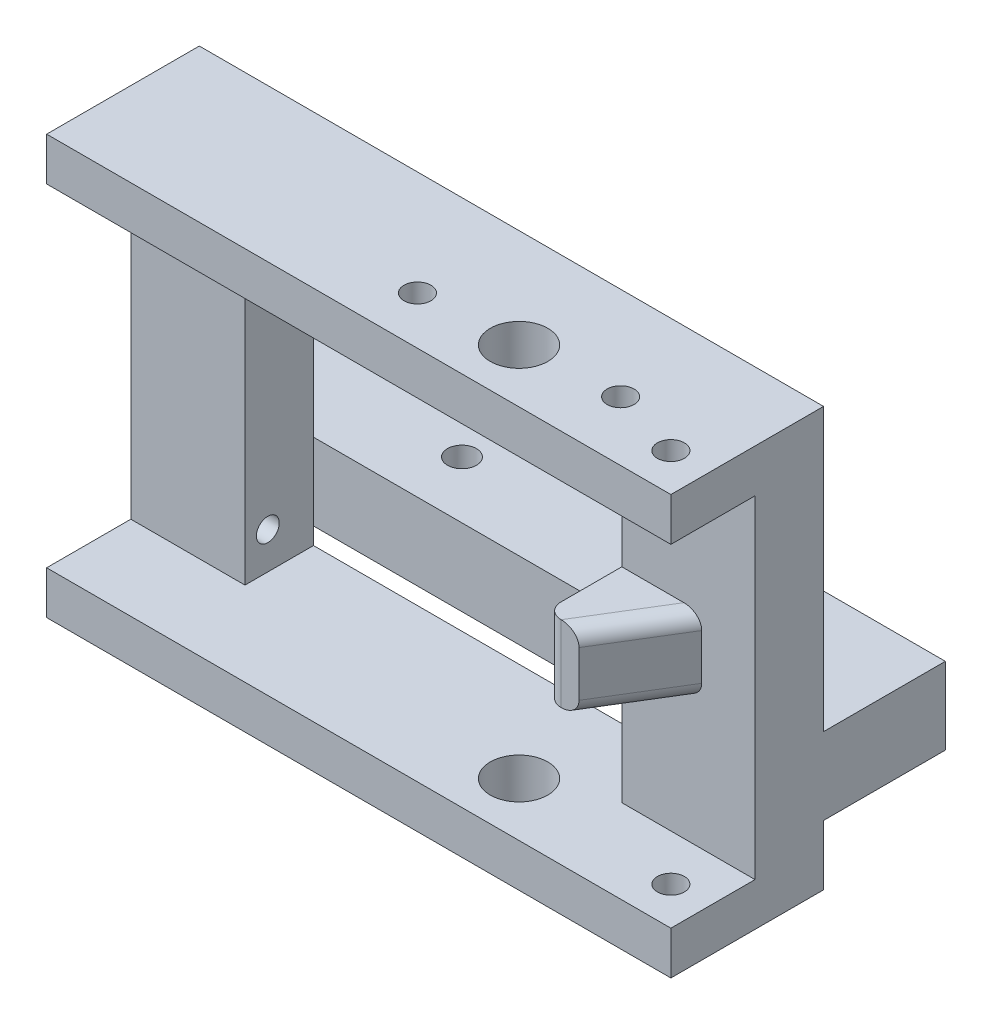
SolidWorks part; units mm, degrees
ref_plane "Front Plane" through (0, 0, 0) normal (0, 0, 1) x (1, 0, 0)
ref_plane "Top Plane" through (0, 0, 0) normal (0, 1, 0) x (1, 0, 0)
ref_plane "Right Plane" through (0, 0, 0) normal (1, 0, 0) x (0, 0, -1)
sketch "Sketch1" plane through (0, 0, 0) normal (0, 0, 1) x (1, 0, 0)
  line L1 (57.15, -34.925) -> (-57.15, -34.925)
  line L2 (57.15, -34.925) -> (57.15, 34.925)
  line L3 (57.15, 34.925) -> (-57.15, 34.925)
  line L4 (-57.15, -34.925) -> (-57.15, 34.925)
  line L5 (57.15, -34.925) -> (-57.15, 34.925) construction
  line L6 (57.15, 34.925) -> (-57.15, -34.925) construction
  point P0 (0, 0)
  dimension "D1" = 69.85
  dimension "D2" = 114.3
extrude "Boss-Extrude1" add sketch "Sketch1" along normal blind 57.15
sketch "Sketch2" plane through (0, 0, 57.15) normal (0, 0, 1) x (1, 0, 0)
  line L0 (-57.15, 34.925) -> (-57.15, -34.925) construction
  line L1 (57.15, -27.725) -> (-57.15, -27.725)
  line L2 (57.15, -27.725) -> (57.15, 27.725)
  line L3 (57.15, 27.725) -> (-57.15, 27.725)
  line L4 (-57.15, -27.725) -> (-57.15, 27.725)
  line L5 (57.15, -27.725) -> (-57.15, 27.725) construction
  line L6 (57.15, 27.725) -> (-57.15, -27.725) construction
  line L7 (57.15, 34.925) -> (-57.15, 34.925) construction
  point P0 (0, 0)
  dimension "D1" = 7.2
extrude "Cut-Extrude2" cut sketch "Sketch2" against normal blind 25.4
sketch "Sketch3" plane through (0, 0, 0) normal (0, 0, -1) x (-1, 0, 0)
  line L0 (-57.15, -34.925) -> (-57.15, 34.925) construction
  line L1 (57.15, 34.925) -> (-57.15, 34.925)
  line L2 (57.15, 34.925) -> (57.15, -12.065)
  line L3 (57.15, -12.065) -> (-57.15, -12.065)
  line L4 (-57.15, 34.925) -> (-57.15, -12.065)
  dimension "D1" = 46.99
extrude "Cut-Extrude3" cut sketch "Sketch3" against normal blind 20.32
sketch "Sketch5" plane through (0, -34.925, 0) normal (0, -1, 0) x (1, 0, 0)
  line L0 (-3.81, 10.79) -> (46.99, 10.79) construction
  line L1 (57.15, 20.32) -> (-57.15, 20.32) construction
  line L2 (57.15, 57.15) -> (57.15, 0) construction
  circle A0 centre (-3.81, 10.79) radius 2.415
  circle A1 centre (46.99, 10.79) radius 2.415
  dimension "D3" = 4.83
  dimension "D4" = 10.16
  dimension "D1" = 9.53
  dimension "D2" = 50.8
sketch "Sketch7" plane through (0, -34.925, 0) normal (0, -1, 0) x (1, 0, 0)
  line L0 (57.15, 57.15) -> (57.15, 0) construction
  line L2 (-57.15, 31.75) -> (57.15, 31.75) construction
  circle A0 centre (31.75, 36.83) radius 4.8
  dimension "D1" = 9.6
  dimension "D2" = 25.4
  dimension "D3" = 5.08
extrude "Cut-Extrude6" cut sketch "Sketch7" against normal up to surface (69.85 mm away) up to face at (0, 34.925, 38.735)
sketch "Sketch8" plane through (0, 34.925, 0) normal (0, 1, 0) x (1, 0, 0)
  line L0 (15.7798, -37.8068) -> (47.7202, -35.8532) construction
  line L1 (57.15, -31.75) -> (-57.15, -31.75) construction
  circle A0 centre (31.75, -36.83) radius 16 construction
  circle A1 centre (15.7798, -37.8068) radius 2.25
  circle A2 centre (47.7202, -35.8532) radius 2.25
  dimension "D1" = 32
  dimension "D2" = 4.5
  dimension "D3" = 3.5
sketch "Sketch9" plane through (0, 0, 31.75) normal (0, 0, 1) x (1, 0, 0)
  line L0 (57.15, 34.925) -> (-57.15, 34.925) construction
  line L5 (57.15, 27.725) -> (-57.15, 27.725) construction
  line L6 (-19.05, 27.725) -> (43.815, 27.725)
  line L7 (-19.05, 27.725) -> (-19.05, -27.725)
  line L8 (-19.05, -27.725) -> (43.815, -27.725)
  line L9 (43.815, 27.725) -> (43.815, -27.725)
  line L10 (-57.15, -27.725) -> (57.15, -27.725) construction
  line L11 (-57.15, 27.725) -> (-57.15, -27.725) construction
  line L12 (57.15, -27.725) -> (57.15, 27.725) construction
  line L13 (-57.15, -34.925) -> (-38.1, -34.925)
  line L14 (-57.15, -34.925) -> (-57.15, 34.925)
  line L15 (-57.15, 34.925) -> (-38.1, 34.925)
  line L16 (-38.1, -34.925) -> (-38.1, 34.925)
  line L17 (-57.15, -34.925) -> (-38.1, 34.925) construction
  line L18 (-57.15, 34.925) -> (-38.1, -34.925) construction
  line L19 (-57.15, -34.925) -> (57.15, -34.925) construction
  point P5 (-47.625, 0)
  dimension "D1" = 13.335
  dimension "25in" = 38.1
  dimension "D2" = 19.05
extrude "Cut-Extrude7" cut sketch "Sketch9" against normal through all both and the other way through all
extrude "Cut-Extrude8" cut sketch "Sketch8" against normal up to next
sketch "Sketch10" [suppressed] plane through (0, 0, 29.21) normal (0, 0, 1) x (1, 0, 0)
  line L1 (-30.607, -1.778) -> (-30.607, -6.604) construction
  circle A0 centre (-33.2489, -4.191) radius 2.286
  point P5 (-30.607, -4.191)
  dimension "D1" = 4.572
sketch "Sketch11" [suppressed] plane through (0, 0, 20.32) normal (0, 0, -1) x (-1, 0, 0)
  circle A0 centre (33.2489, -4.191) radius 2.286
  dimension "D1" = 4.572
extrude "Cut-Extrude9" [suppressed] cut sketch "Sketch11" against normal blind 3.81
sketch "Sketch12" plane through (-19.05, 0, 0) normal (1, 0, 0) x (0, 0, -1)
  line L0 (-31.75, -27.725) -> (-31.75, 27.725) construction
  line L1 (-27.94, -21.59) -> (-27.94, 21.59) construction
  line L2 (-20.32, 27.725) -> (-20.32, -12.065) construction
  circle A0 centre (-27.94, -21.59) radius 1.905
  circle A1 centre (-27.94, 21.59) radius 1.905
  point P0 (-31.75, 0)
  point P8 (-27.94, 0)
  dimension "D1" = 3.81
  dimension "D2" = 7.62
  dimension "D3" = 43.18
extrude "Cut-Extrude10" cut sketch "Sketch12" against normal up to surface (19.05 mm away) up to face at (-38.1, -2.413, 33.274)
sketch "Sketch13" plane through (0, 34.925, 0) normal (0, 1, 0) x (1, 0, 0)
  line L0 (-38.1, -45.7884) -> (57.15, -45.7884)
  line L2 (57.15, -57.15) -> (-38.1, -57.15) construction
  line L3 (47.7202, -35.8532) -> (15.7798, -37.8068) construction
  line L4 (-38.1, -45.7884) -> (-38.1, -57.15)
  line L5 (-38.1, -57.15) -> (57.15, -57.15)
  line L6 (-38.1, -20.32) -> (-38.1, -57.15) construction
  line L7 (57.15, -57.15) -> (57.15, -20.32) construction
  line L8 (57.15, -45.7884) -> (57.15, -57.15)
extrude "Cut-Extrude12" cut sketch "Sketch13" against normal through all
sketch "Sketch14" plane through (43.815, 0, 0) normal (-1, 0, 0) x (0, 0, 1)
  line L0 (0, -27.725) -> (31.75, -27.725) construction
  line L1 (20.32, -12.065) -> (0, -12.065)
  line L2 (20.32, -12.065) -> (20.32, -27.725)
  line L3 (20.32, -27.725) -> (0, -27.725)
  line L4 (0, -12.065) -> (0, -27.725)
extrude "Boss-Extrude2" add sketch "Sketch14" along normal up to next
sketch "Sketch16" plane through (0, 0, 31.75) normal (0, 0, 1) x (1, 0, 0)
  line L0 (43.815, -27.725) -> (43.815, 27.725) construction
  line L1 (57.15, -6.35) -> (43.815, -6.35)
  line L2 (57.15, -6.35) -> (57.15, 6.35)
  line L3 (57.15, 6.35) -> (43.815, 6.35)
  line L4 (43.815, -6.35) -> (43.815, 6.35)
  line L5 (57.15, -6.35) -> (43.815, 6.35) construction
  line L6 (57.15, 6.35) -> (43.815, -6.35) construction
  line L7 (57.15, 6.35) -> (57.15, -6.35) construction
  line L9 (57.15, -27.725) -> (57.15, 27.725) construction
  point P0 (50.4825, 0)
  point P7 (57.15, 0)
  dimension "D1" = 12.7
extrude "Boss-Extrude3" add sketch "Sketch16" along normal blind 12.7
sketch "Sketch17" plane through (0, 6.35, 0) normal (0, 1, 0) x (1, 0, 0)
  line L0 (49.375, -44.45) -> (57.15, -31.75)
  line L1 (57.15, -44.45) -> (57.15, -31.75) construction
  line L2 (57.15, -31.75) -> (43.815, -31.75) construction
  line L3 (57.15, -31.75) -> (57.15, -44.45)
  line L4 (57.15, -44.45) -> (49.375, -44.45)
  line L5 (57.15, -44.45) -> (43.815, -44.45) construction
extrude "Cut-Extrude14" cut sketch "Sketch17" against normal blind 12.7
fillet "Fillet4" radius 2.54 2 edges at (53.2625, -6.35, 38.1) (53.2625, 6.35, 38.1)
sketch "Sketch18" plane through (-38.1, 0, 0) normal (-1, 0, 0) x (0, 0, 1)
  line L0 (0, -34.925) -> (45.7884, -34.925) construction
  line L1 (20.32, -35.0627) -> (20.32, -24.9001)
  line L2 (20.32, -24.9001) -> (0, -24.9001)
  line L3 (0, -34.925) -> (0, -12.065) construction
  line L4 (0, -24.9001) -> (0, -34.925)
  line L5 (20.32, -34.925) -> (0, -34.925)
  point P0 (20.32, -34.925)
  point P1 (7.9478, 3.6724)
  line M3 (0, -34.925) -> (45.7884, -34.925)
  line M12 (0, -12.065) -> (0, -34.925)
sketch "Sketch19" plane through (-38.1, 0, 0) normal (-1, 0, 0) x (0, 0, 1)
  line L0 (20.32, -34.925) -> (0, -34.925)
sketch "Sketch20" plane through (-38.1, 0, 0) normal (-1, 0, 0) x (0, 0, 1)
  line L0 (0, -34.925) -> (45.7884, -34.925) construction
  line L1 (20.066, -34.925) -> (20.066, -24.765)
  line L2 (20.066, -24.765) -> (0, -24.765)
  line L3 (0, -34.925) -> (0, -12.065) construction
  line L4 (0, -24.765) -> (0, -34.925)
  line L5 (20.066, -34.925) -> (-0.1509, -34.925)
  point P0 (20.32, -34.925)
  dimension "D1" = 10.16
  dimension "D2" = 20.066
extrude "Cut-Extrude20" cut sketch "Sketch5" against normal through all contours A0 | A1
sketch "Sketch21" plane through (-38.1, 0, 0) normal (-1, 0, 0) x (0, 0, 1)
sketch "Sketch22" plane through (-38.1, 0, 0) normal (-1, 0, 0) x (0, 0, 1)
extrude "Cut-Extrude21" cut sketch "Sketch18" against normal through all contours L1 L2 M12 M3 region at (-38.1, -29.9125, 10.16)
sketch "Sketch23" plane through (0, -34.925, 0) normal (0, -1, 0) x (1, 0, 0)
  line L0 (57.15, 20.32) -> (57.15, 31.75)
  line L1 (57.15, 45.7884) -> (57.15, 20.32) construction
  circle A0 centre (52.07, 26.035) radius 2.413
  point P7 (57.15, 26.035)
  dimension "D2" = 4.826
  dimension "D1" = 11.43
  dimension "D3" = 5.08
sketch "Sketch24" plane through (0, 34.925, 0) normal (0, 1, 0) x (1, 0, 0)
  line L0 (47.7202, -35.8532) -> (15.7798, -37.8068)
  point P0 (47.7202, -35.8532)
  point P1 (15.7798, -37.8068)
sketch3d "3DSketch2"
  line L1 (47.7202, 34.925, 35.8532) -> (15.7798, 34.925, 37.8068) construction
fillet "Fillet5" radius 2.54 1 edges at (43.815, 0, 44.45)
sketch "Sketch26" plane through (57.15, 0, 0) normal (1, 0, 0) x (0, 0, -1)
  line L28 (-45.7884, -34.925) -> (-20.32, -34.925)
  line L29 (-20.32, -34.925) -> (-20.32, -24.9001)
  line L30 (-20.32, -24.9001) -> (0, -24.9001)
  line L31 (0, -24.9001) -> (0, -12.065)
  line L32 (0, -12.065) -> (-20.32, -12.065)
  line L33 (-20.32, -12.065) -> (-20.32, 34.925)
  line L34 (-20.32, 34.925) -> (-45.7884, 34.925)
  line L35 (-45.7884, 34.925) -> (-45.7884, 27.725)
  line L36 (-45.7884, 27.725) -> (-31.75, 27.725)
  line L37 (-31.75, 27.725) -> (-31.75, 3.81)
  line L38 (-31.75, 3.81) -> (-31.75, -3.81)
  line L39 (-31.75, -3.81) -> (-31.75, -27.725)
  line L40 (-31.75, -27.725) -> (-45.7884, -27.725)
  line L41 (-45.7884, -27.725) -> (-45.7884, -34.925)
  line L42 (-45.7884, -34.925) -> (-20.32, -34.925)
  line L43 (-20.32, -34.925) -> (-20.32, -24.9001)
  line L44 (-20.32, -24.9001) -> (0, -24.9001)
  line L45 (0, -24.9001) -> (0, -12.065)
  line L46 (0, -12.065) -> (-20.32, -12.065)
  line L47 (-20.32, -12.065) -> (-20.32, 34.925)
  line L48 (-20.32, 34.925) -> (-45.7884, 34.925)
  line L49 (-45.7884, 34.925) -> (-45.7884, 27.725)
  line L50 (-45.7884, 27.725) -> (-31.75, 27.725)
  line L51 (-31.75, 27.725) -> (-31.75, 3.81)
  line L52 (-31.75, 3.81) -> (-31.75, -3.81)
  line L53 (-31.75, -3.81) -> (-31.75, -27.725)
  line L54 (-31.75, -27.725) -> (-45.7884, -27.725)
  line L55 (-45.7884, -27.725) -> (-45.7884, -34.925)
  dimension "D1" = 0
extrude "Boss-Extrude4" add sketch "Sketch26" along normal blind 8.89
sketch "Sketch31" plane through (0, 34.925, 0) normal (0, 1, 0) x (1, 0, 0)
  line L0 (66.04, -45.7884) -> (-38.1, -45.7884) construction
  line L1 (66.04, -20.32) -> (66.04, -45.7884) construction
  point P0 (59.69, -39.4384)
  dimension "D1" = 6.35
  dimension "D2" = 6.35
hole_wizard "#8 Clearance Hole1" positions "Sketch31" profile "Sketch30" hole size "#8" standard "ANSI Inch" end condition through all
sketch "Sketch30" plane through (59.69, 34.925, 39.4384) normal (1, 0, 0) x (0, 0, 1)
  line L0 (0, 0) -> (0, 69.85)
  line L1 (0, 69.85) -> (2.2479, 69.85)
  line L2 (2.2479, 69.85) -> (2.2479, 0)
  line L5 (2.2479, 0) -> (0, 0)
  line L11 (0, -6.35) -> (0, 107.95) construction
  dimension "Thru Hole Dia." = 4.4958
  dimension "Thru Hole Depth" = 69.85
